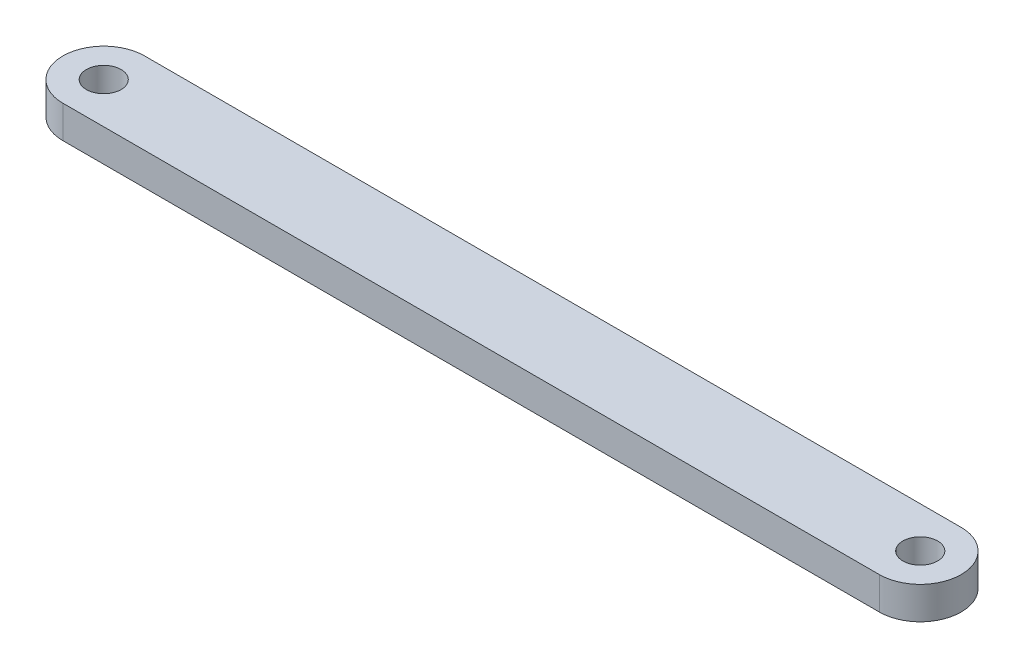
SolidWorks part; units mm, degrees
material "Acrylic (Medium-high impact)"
ref_plane "Front Plane" through (0, 0, 0) normal (0, 0, 1) x (1, 0, 0)
ref_plane "Top Plane" through (0, 0, 0) normal (0, 1, 0) x (1, 0, 0)
ref_plane "Right Plane" through (0, 0, 0) normal (1, 0, 0) x (0, 0, -1)
sketch "Sketch1" plane through (0, 0, 0) normal (0, 1, 0) x (1, 0, 0)
  line L0 (40.0183, 4.0001) -> (-39.84, 4.0001)
  line L1 (-39.84, -4.0001) -> (40.0183, -4.0001)
  arc A0 (-39.84, 4.0001) -> (-39.84, -4.0001) centre (-39.84, 0) ccw
  arc A1 (40.0183, -4.0001) -> (40.0183, 4.0001) centre (40.0183, 0) ccw
  circle A2 centre (-39.84, 0) radius 1.7
  circle A3 centre (40.0183, 0) radius 1.7
  dimension "D1" = 3.4
extrude "Boss-Extrude1" add sketch "Sketch1" along normal blind 3.175
